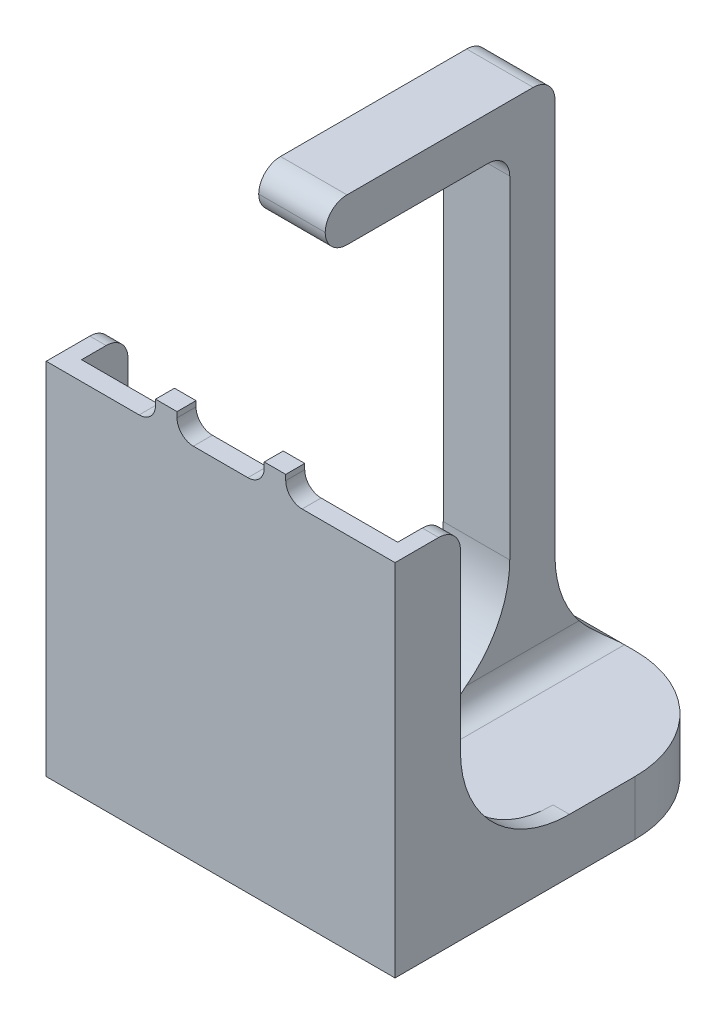
SolidWorks part; units mm, degrees
ref_plane "Front Plane" through (0, 0, 0) normal (0, 0, 1) x (1, 0, 0)
ref_plane "Top Plane" through (0, 0, 0) normal (0, 1, 0) x (1, 0, 0)
ref_plane "Right Plane" through (0, 0, 0) normal (1, 0, 0) x (0, 0, -1)
sketch "Sketch1" plane through (0, 0, 0) normal (0, 1, 0) x (1, 0, 0)
  line L4 (16, -16) -> (-16, -16)
  line L5 (16, -16) -> (16, 16)
  line L6 (16, 16) -> (-16, 16)
  line L7 (-16, -16) -> (-16, 16)
  line L8 (16, -16) -> (-16, 16) construction
  line L9 (16, 16) -> (-16, -16) construction
extrude "Boss-Extrude1" add sketch "Sketch1" along normal blind 5
sketch "Sketch2" plane through (0, 5, 0) normal (0, 1, 0) x (1, 0, 0)
  line L0 (0, -16) -> (-14.5, -16)
  line L1 (-16, -16) -> (16, -16) construction
  line L2 (0, -16) -> (14.5, -16)
  line L3 (-14.5, -14.257) -> (-14.5, -10)
  line L4 (-14.5, -10) -> (-16, -10)
  line L5 (-16, 16) -> (-16, -16) construction
  line L6 (-16, -10) -> (-16, -16)
  line L7 (-16, -16) -> (-14.5, -16)
  line L8 (-14.5, -14.257) -> (14.5, -14.257)
  line L9 (14.5, -14.257) -> (14.5, -10)
  line L10 (14.5, -10) -> (16, -10)
  line L11 (16, -16) -> (16, 16) construction
  line L12 (16, -10) -> (16, -16)
  line L13 (16, -16) -> (14.5, -16)
  line L14 (0, -14.257) -> (0, -9.457)
  line L15 (0, -9.457) -> (-3.05, -9.457)
  line L16 (0, -9.457) -> (3.05, -9.457)
  line L17 (3.05, -9.457) -> (3.05, -5.4516)
  line L18 (3.05, -5.4516) -> (-3.05, -5.4516)
  line L19 (-3.05, -5.4516) -> (-3.05, -9.457)
  line M4 (-16, 16) -> (-16, -16)
  line M5 (-16, -16) -> (16, -16)
  line M6 (16, -16) -> (16, 16)
extrude "Boss-Extrude5" add sketch "Sketch2" along normal blind 28 contours L18 L19 L15 L16 L17 | L10 L9 L8 L3 L4 M4 M5 M6 region at (0, 5, 7.4543) region at (0, 5, 14.5696)
sketch "Sketch6" plane through (0, 33, 0) normal (0, 1, 0) x (1, 0, 0)
  line L1 (-3.05, -5.4516) -> (3.05, -5.4516)
  line L2 (-3.05, -5.4516) -> (-3.05, -9.457)
  line L3 (-3.05, -9.457) -> (3.05, -9.457)
  line L4 (3.05, -5.4516) -> (3.05, -9.457)
extrude "Cut-Extrude2" cut sketch "Sketch6" against normal blind 24
sketch "Sketch7" plane through (0, 0, 16) normal (0, 0, 1) x (1, 0, 0)
  line L1 (-16, 33) -> (16, 33) construction
  line L2 (-4, 33) -> (-4, 35)
  line L3 (-4, 35) -> (-5.9737, 35)
  line L4 (-5.9737, 35) -> (-5.9737, 33)
  line L6 (-4, 33) -> (-5.9737, 33)
  line L7 (4, 33) -> (5.9737, 33)
  line L8 (5.9737, 35) -> (5.9737, 33)
  line L9 (4, 35) -> (5.9737, 35)
  line L10 (4, 33) -> (4, 35)
extrude "Boss-Extrude6" add sketch "Sketch7" against normal up to surface (1.743 mm away) up to face at (0, 19, 14.257)
fillet "Fillet1" radius 1.5 4 edges at (5.9737, 33, 15.1285) (-5.9737, 33, 15.1285) (-4, 33, 15.1285) (4, 33, 15.1285)
sketch "Sketch8" plane through (0, 5, 0) normal (0, 1, 0) x (1, 0, 0)
  line L3 (3.05, 11.6229) -> (-3.05, 11.6229)
  line L4 (3.05, 11.6229) -> (3.05, 7.4739)
  line L5 (3.05, 7.4739) -> (-3.05, 7.4739)
  line L6 (-3.05, 11.6229) -> (-3.05, 7.4739)
  line L7 (3.05, 11.6229) -> (-3.05, 7.4739) construction
  line L8 (3.05, 7.4739) -> (-3.05, 11.6229) construction
extrude "Boss-Extrude7" add sketch "Sketch8" along normal blind 42.5
sketch "Sketch9" plane through (0, 0, -7.4739) normal (0, 0, 1) x (1, 0, 0)
  line L1 (3.05, 47.5) -> (-3.05, 47.5)
  line L2 (3.05, 47.5) -> (3.05, 51.4724)
  line L3 (3.05, 51.4724) -> (-3.05, 51.4724)
  line L4 (-3.05, 47.5) -> (-3.05, 51.4724)
extrude "Boss-Extrude8" add sketch "Sketch9" along normal up to surface (16.9309 mm away) separate body up to face at (0, 7, 9.457)
sketch "Sketch10" plane through (0, 0, -7.4739) normal (0, 0, -1) x (-1, 0, 0)
  line L1 (-3.05, 51.4724) -> (3.05, 51.4724)
  line L2 (-3.05, 51.4724) -> (-3.05, 47.5)
  line L3 (-3.05, 47.5) -> (3.05, 47.5)
  line L4 (3.05, 51.4724) -> (3.05, 47.5)
extrude "Boss-Extrude9" add sketch "Sketch10" along normal up to surface (4.149 mm away) up to face at (0, 26.25, -11.6229)
fillet "Fillet3" radius 2 8 edges at (0, 51.4724, -11.6229) (0, 47.5, -7.4739) (0, 47.5, 9.457) (0, 51.4724, 9.457) (0, 9, 9.457) (0, 9, 5.4516) (-15.25, 33, 10) (15.25, 33, 10)
fillet "Fillet5" radius 10 4 edges at (0, 5, -7.4739) (15.25, 5, 10) (-15.25, 5, 10) (0, 5, -11.6229)
fillet "Fillet6" radius 2 4 edges at (-3.05, 5, -6.7369) (-3.05, 5, 7.4543) (3.05, 5, -6.7369) (3.05, 5, 7.4543)
fillet "Fillet7" radius 10 2 edges at (16, 2.5, -16) (-16, 2.5, -16)
